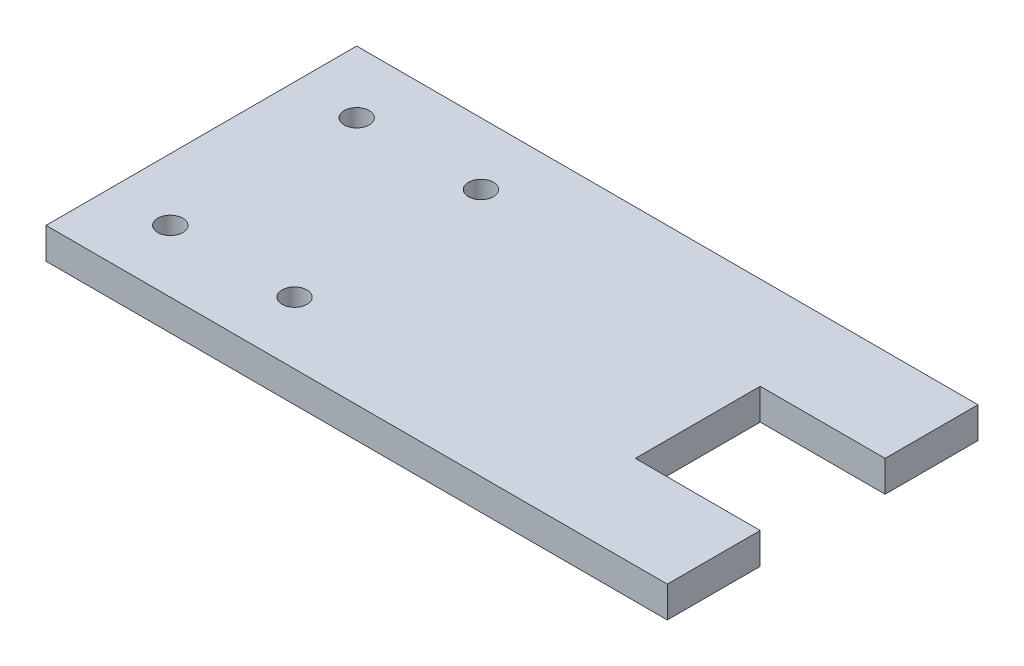
SolidWorks part; units mm, degrees
ref_plane "Front Plane" through (0, 0, 0) normal (0, 0, 1) x (1, 0, 0)
ref_plane "Top Plane" through (0, 0, 0) normal (0, 1, 0) x (1, 0, 0)
ref_plane "Right Plane" through (0, 0, 0) normal (1, 0, 0) x (0, 0, -1)
sketch "Sketch1" plane through (0, 0, 0) normal (0, 1, 0) x (1, 0, 0)
  line L0 (50.8, 31.75) -> (76.2, 31.75)
  line L1 (-50.8, -31.75) -> (50.8, -31.75)
  line L2 (-50.8, -31.75) -> (-50.8, 31.75)
  line L3 (-50.8, 31.75) -> (50.8, 31.75)
  line L5 (-50.8, -31.75) -> (50.8, 31.75) construction
  line L6 (-50.8, 31.75) -> (50.8, -31.75) construction
  line L7 (76.2, 31.75) -> (76.2, -31.75)
  line L8 (76.2, -31.75) -> (50.8, -31.75)
  point P0 (0, 0)
  dimension "D1" = 101.6
  dimension "D2" = 63.5
  dimension "D3" = 25.4
extrude "Boss-Extrude1" add sketch "Sketch1" along normal blind 6.35
sketch "Sketch2" plane through (0, 6.35, 0) normal (0, 1, 0) x (1, 0, 0)
  line L4 (76.2, 31.75) -> (-50.8, 31.75) construction
  line L5 (-50.8, -31.75) -> (76.2, -31.75) construction
  line L7 (0, 31.75) -> (0, -31.75) construction
  line L8 (-50.8, 31.75) -> (-50.8, -31.75) construction
  dimension "D1" = 50.8
hole_wizard "#10 Clearance Hole1" positions "Sketch3" profile "Sketch4" hole size "#10" standard "ANSI Inch" end condition through all
sketch "Sketch3" plane through (0, 6.35, 0) normal (0, 1, 0) x (1, 0, 0)
  line L4 (-38.1, 31.75) -> (-38.1, -31.75) construction
  line L5 (76.2, 31.75) -> (-50.8, 31.75) construction
  line L6 (-50.8, -31.75) -> (76.2, -31.75) construction
  line L8 (-12.7, 31.75) -> (-12.7, -31.75) construction
  line L9 (-50.8, 31.75) -> (-50.8, -31.75) construction
  line L11 (-50.8, 19.05) -> (0, 19.05) construction
  line L13 (-50.8, -19.05) -> (0, -19.05) construction
  point P0 (-38.1, 19.05)
  point P2 (-12.7, 19.05)
  point P4 (-12.7, -19.05)
  point P6 (-38.1, -19.05)
  dimension "D1" = 12.7
  dimension "D2" = 38.1
  dimension "D3" = 12.7
  dimension "D4" = 12.7
  dimension "D5" = 50.8
  dimension "D6" = 50.8
sketch "Sketch4" plane through (-38.1, 6.35, -19.05) normal (1, 0, 0) x (0, 0, 1)
  line L0 (0, 0) -> (0, 6.35)
  line L1 (0, 6.35) -> (2.5527, 6.35)
  line L2 (2.5527, 6.35) -> (2.5527, 0)
  line L5 (2.5527, 0) -> (0, 0)
  line L11 (0, -6.35) -> (0, 107.95) construction
  dimension "Thru Hole Dia." = 5.1054
  dimension "Thru Hole Depth" = 6.35
sketch "Sketch5" plane through (0, 6.35, 0) normal (0, 1, 0) x (1, 0, 0)
  line L1 (76.2, -31.75) -> (76.2, 31.75) construction
  line L2 (50.673, -12.7635) -> (76.2, -12.7635)
  line L4 (50.673, -12.7635) -> (50.673, 12.7635)
  line L5 (50.673, 12.7635) -> (76.2, 12.7635)
  line L6 (76.2, -12.7635) -> (76.2, 12.7635)
  line L7 (50.673, -12.7635) -> (76.2, 12.7635) construction
  line L8 (50.673, 12.7635) -> (76.2, -12.7635) construction
  line L13 (76.2, 12.7635) -> (76.2, 31.75) construction
  line L14 (76.2, -12.7635) -> (76.2, -31.75) construction
  dimension "D3" = 25.527
extrude "Cut-Extrude1" cut sketch "Sketch5" against normal through all
